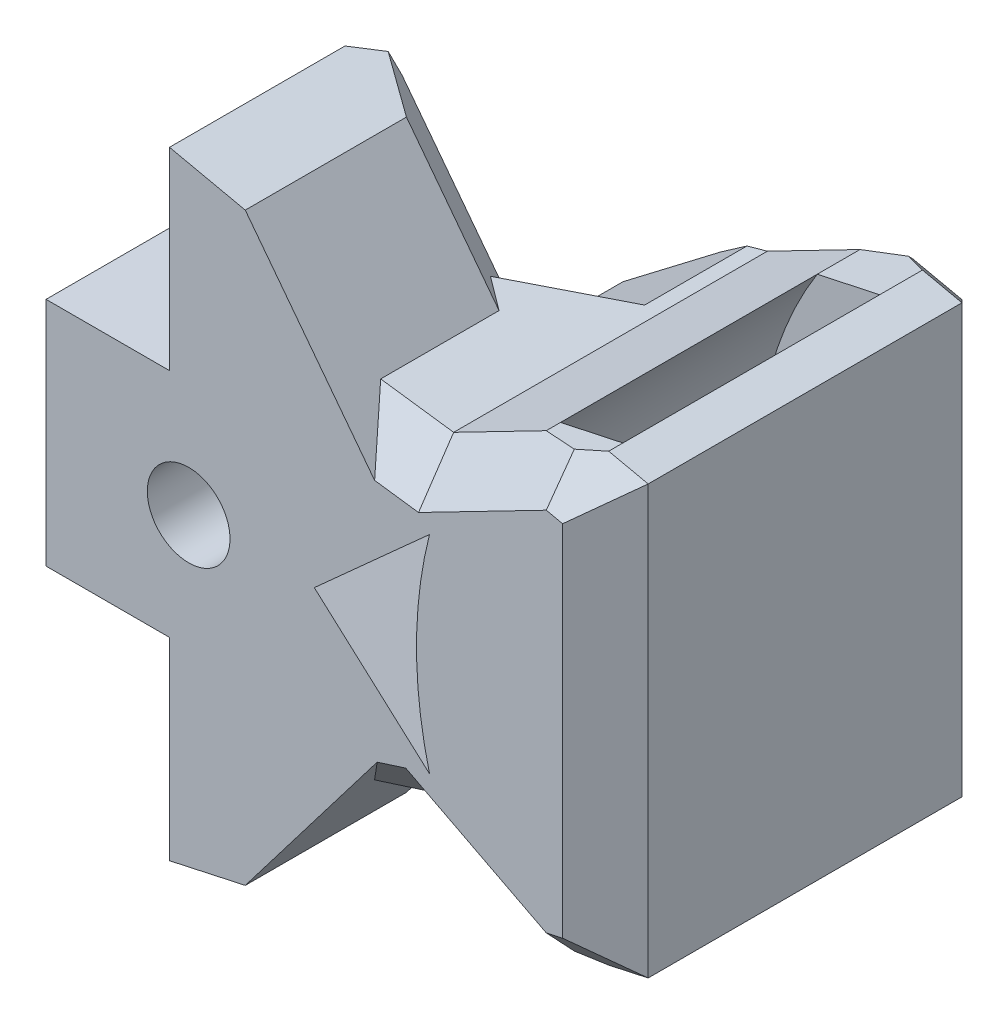
SolidWorks part; units mm, degrees
ref_plane "Alzado" through (0, 0, 0) normal (0, 0, 1) x (1, 0, 0)
ref_plane "Planta" through (0, 0, 0) normal (0, 1, 0) x (1, 0, 0)
ref_plane "Vista lateral" through (0, 0, 0) normal (1, 0, 0) x (0, 0, -1)
sketch "Croquis1" plane through (0, 0, 0) normal (0, 0, 1) x (1, 0, 0)
  line L0 (29.7, -10.8304) -> (29.7, -4.05)
  line L1 (29.7, -4.05) -> (25.3722, -4.05)
  line L2 (25.3722, -4.05) -> (25.3722, 4.05)
  line L3 (25.3722, 4.05) -> (29.7, 4.05)
  line L4 (29.7, 4.05) -> (29.7, 10.8304)
  line L5 (29.7, 10.8304) -> (44.9816, 7.5)
  line L6 (44.9816, 7.5) -> (44.9816, -7.5)
  line L7 (44.9816, -7.5) -> (29.7, -10.8304)
  line L8 (29.6, -4.15) -> (29.6, -10.8298) construction
  line L9 (11.14, -4.15) -> (28.6, -4.15) construction
  line L10 (30.3722, 0) -> (25.3722, 0) construction
  line L11 (25.3722, 0) -> (20.3722, 0) construction
  line L12 (30.3722, 0) -> (44.9816, 0) construction
  line L14 (42.6, 10.3) -> (42.6, -10.3) construction
  circle A0 centre (30.3722, 0) radius 1.45
  circle A1 centre (30.3722, 0) radius 1.45 construction
  circle A2 centre (55.6, 0) radius 13 construction
  dimension "D3" = 26
  dimension "D1" = 0.1
  dimension "D2" = 0.1
  dimension "D4" = 15
extrude "Saliente-Extruir1" add sketch "Croquis1" along normal blind 13
ref_plane "Plano1" through (0, 0, 6.5) normal (0, 0, -1) x (-1, 0, 0)
sketch "Croquis2" plane through (0, 0, 6.5) normal (0, 0, -1) x (-1, 0, 0)
  line L0 (-30.3722, 0) -> (-53.0411, 0) construction
  circle A0 centre (-53.0411, 0) radius 13 construction
  circle A1 centre (-53.0411, 0) radius 12.25
  circle A2 centre (-53.0411, 0) radius 13.75
  dimension "D1" = 26
  dimension "D2" = 0.75
  dimension "D3" = 0.75
extrude "CorteSelfieStick" cut sketch "Croquis2" against normal blind 4.5 and the other way blind 4.5
sketch "Croquis3" plane through (0, 0, 13) normal (0, 0, 1) x (1, 0, 0)
  line L0 (32.3564, 10.2515) -> (36.5143, 4.8074)
  line L1 (44.9816, 7.5) -> (29.7, 10.8304) construction
  line L2 (36.5143, 4.8074) -> (42.7008, 7.9971)
  line L3 (34.7766, 0) -> (38.8159, 3.6328)
  line L5 (38.8159, -3.6328) -> (34.7766, 0)
  line L6 (30.3722, 0) -> (34.7766, 0) construction
  line L7 (34.7766, 0) -> (38.2455, 0) construction
  line L8 (32.3564, 10.2515) -> (42.7008, 7.9971)
  line L9 (32.3564, -10.2515) -> (36.5143, -4.8074)
  line L10 (36.5143, -4.8074) -> (42.7008, -7.9971)
  line L11 (32.3564, -10.2515) -> (42.7008, -7.9971)
  line L12 (38.8159, 3.6328) -> (38.8159, 0) construction
  line L13 (38.8159, 0) -> (38.8159, -3.6328) construction
  line L14 (38.8159, 0) -> (38.2455, 0) construction
  arc A0 (38.8159, 3.6328) -> (38.8159, -3.6328) centre (53.0411, 0) ccw
extrude "Cortar-Extruir1" cut sketch "Croquis3" against normal through all
sketch "Croquis4" plane through (0, 0, 0) normal (0, 0, -1) x (-1, 0, 0)
  line L0 (-25.3722, 4.05) -> (-29.7, 4.05)
  line L1 (-29.7, 4.05) -> (-29.7, 10.8304)
  line L2 (-29.7, 10.8304) -> (-32.3564, 10.2515)
  line L3 (-32.3564, 1.6319) -> (-32.3564, -1.6319)
  line L4 (-32.3564, -10.2515) -> (-29.7, -10.8304)
  line L5 (-29.7, -10.8304) -> (-29.7, -4.05)
  line L6 (-29.7, -4.05) -> (-25.3722, -4.05)
  line L7 (-32.3564, 10.2515) -> (-36.5143, 4.8074)
  line L8 (-36.5143, 4.8074) -> (-32.3564, 1.6319)
  line L9 (-32.3564, 1.6319) -> (-32.3564, -1.6319)
  line L10 (-32.3564, -1.6319) -> (-36.5143, -4.8074)
  line L11 (-36.5143, -4.8074) -> (-32.3564, -10.2515)
  line L12 (-32.3564, 10.2515) -> (-36.5143, 4.8074)
  line L13 (-25.3722, 4.05) -> (-25.3722, -4.05)
  line L14 (-32.3564, 10.2515) -> (-32.3564, 1.6319) construction
  line M9 (-36.5143, -4.8074) -> (-32.3564, -10.2515)
  line M10 (-32.3564, -10.2515) -> (-29.7, -10.8304)
  line M11 (-29.7, -10.8304) -> (-29.7, -4.05)
  line M12 (-29.7, -4.05) -> (-25.3722, -4.05)
  line M13 (-25.3722, -4.05) -> (-25.3722, 4.05)
  line M14 (-25.3722, 4.05) -> (-29.7, 4.05)
  line M15 (-29.7, 4.05) -> (-29.7, 10.8304)
  line M16 (-29.7, 10.8304) -> (-32.3564, 10.2515)
  line M17 (-32.3564, 10.2515) -> (-36.5143, 4.8074)
  circle M21 centre (-30.3722, 0) radius 1.45
extrude "Cortar-Extruir2" cut sketch "Croquis4" against normal up to surface (5.85 mm away) contours L14 L3 L10 M16 M9 M10 M11 M12 M13 M14 M15 M21 | L14 L8 M17 region at (25.6158, 0, 0) region at (33.7424, 5.5636, 0)
chamfer "Chaflán1" distance 0.5 angle 45 11 edges at (36.7963, 1.8164, 0) (38.3594, 0, 0) (36.7963, -1.8164, 0) (32.3564, 0, 0) (34.4354, -3.2196, 0) (39.6075, -6.4022, 0) (43.8412, -7.7485, 0) (44.9816, 0, 0) (43.8412, 7.7485, 0) (39.6075, 6.4022, 0) (34.4354, 3.2196, 0)
chamfer "Chaflán2" distance 1.5 angle 45 4 edges at (36.5143, -4.8074, 9.425) (36.5143, 4.8074, 9.425) (34.4354, 3.2196, 5.85) (34.4354, -3.2196, 5.85) first distance on face at (40.3514, -6.7857, 6.5389) first distance on face at (34.4354, 7.5294, 9.425) first distance on face at (34.4354, 3.2196, 3.175) first distance on face at (34.4354, -3.2196, 3.175)
chamfer "Chaflán4" distance 1.5 angle 45 9 edges at (33.8728, -8.266, 5.85) (33.9801, 8.1255, 5.85) (36.8828, 5.8282, 13) (36.6184, -5.8876, 13) (40.2741, -6.7459, 13) (40.4313, 6.827, 13) (43.8412, 7.7485, 13) (43.8412, -7.7485, 13) (44.9816, 0, 13)
sketch "Croquis6" plane through (0, 0, 2) normal (0, 0, 1) x (1, 0, 0)
  line L6 (43.5968, -7.8018) -> (42.7008, -7.9971)
  line L7 (42.7008, -7.9971) -> (41.4081, -7.3306)
  line L8 (41.4081, -7.3306) -> (43.5968, -7.8018)
  line L9 (43.5968, 7.8018) -> (42.7008, 7.9971)
  line L10 (42.7008, 7.9971) -> (41.4081, 7.3306)
  line L11 (41.4081, 7.3306) -> (43.5968, 7.8018)
extrude "Cortar-Extruir3" cut sketch "Croquis6" against normal through all both and the other way through all
chamfer "Chaflán5" distance 1 angle 45 4 edges at (27.5361, -4.05, 5.85) (29.7, -7.4402, 5.85) (27.5361, 4.05, 5.85) (29.7, 7.4402, 5.85)
sketch "Croquis7" plane through (0, 0, 5.85) normal (0, 0, -1) x (-1, 0, 0)
  circle A0 centre (-30.3722, 0) radius 3.5
  dimension "D1" = 7
extrude "Cortar-Extruir4" cut sketch "Croquis7" against normal blind 2 and the other way through all
